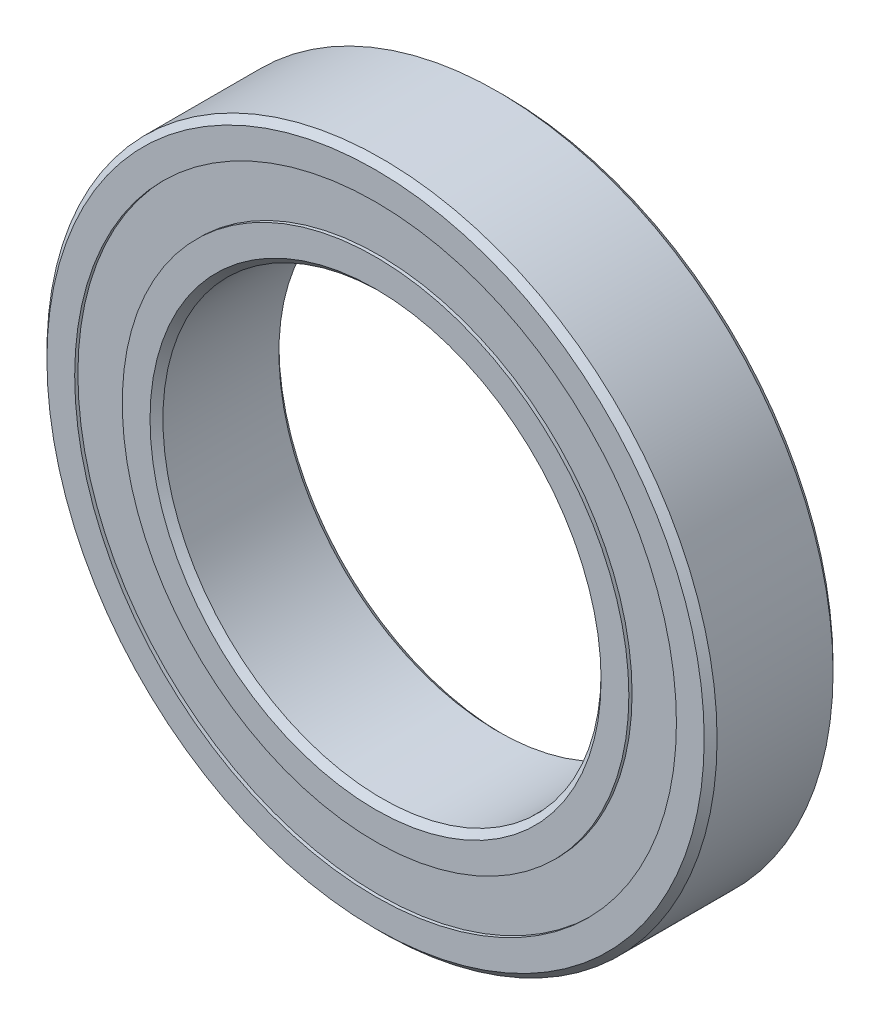
SolidWorks part; units mm, degrees
ref_plane "Front Plane" through (0, 0, 0) normal (0, 0, 1) x (1, 0, 0)
ref_plane "Top Plane" through (0, 0, 0) normal (0, 1, 0) x (1, 0, 0)
ref_plane "Right Plane" through (0, 0, 0) normal (1, 0, 0) x (0, 0, -1)
sketch "Sketch1" plane through (0, 0, 0) normal (0, 0, 1) x (1, 0, 0)
  circle A0 centre (0, 0) radius 13 construction
  circle A1 centre (0, 0) radius 8.5 construction
  dimension "OD" = 26
  dimension "Shaft Dia" = 17
sketch "Sketch2" plane through (0, 0, 0) normal (1, 0, 0) x (0, 0, -1)
  line L0 (-2.5, 0) -> (2.5, 0) construction
  line L1 (0, 13) -> (0, -13) construction
  line L2 (2.25, 13) -> (-2.25, 13) construction
  line L3 (-2.25, 13) -> (-2.5, 12.75) construction
  line L4 (-2.5, 12.75) -> (-2.5, 11.6731) construction
  line L5 (-2.5, 11.6731) -> (-1.1111, 11.6731) construction
  line L6 (2.5, 11.6731) -> (1.1111, 11.6731) construction
  line L7 (2.5, 12.75) -> (2.5, 11.6731) construction
  line L8 (2.25, 13) -> (2.5, 12.75) construction
  line L9 (0, 13) -> (0, 10.75) construction
  line L10 (0, 10.75) -> (0, 8.5) construction
  line L11 (2.5, 10.75) -> (-2.5, 10.75) construction
  line L12 (-2.5, 8.75) -> (-2.5, 9.8269) construction
  line L13 (-2.25, 8.5) -> (-2.5, 8.75) construction
  line L14 (2.25, 8.5) -> (-2.25, 8.5) construction
  line L15 (2.25, 8.5) -> (2.5, 8.75) construction
  line L16 (2.5, 8.75) -> (2.5, 9.8269) construction
  line L17 (2.5, 9.8269) -> (1.1111, 9.8269) construction
  line L18 (-2.5, 9.8269) -> (-1.1111, 9.8269) construction
  arc A0 (-1.1111, 11.6731) -> (1.1111, 11.6731) centre (0, 10.75) cw construction
  arc A1 (-1.1111, 9.8269) -> (1.1111, 9.8269) centre (0, 10.75) ccw construction
  point P14 (0, 8.5)
  point P18 (0, 10.75)
  dimension "D1" = 45
  dimension "D2" = 0.25
  dimension "D3" = 2.2222
  dimension "D4" = 0.9231
  dimension "Width" = 5
sketch "Sketch6" plane through (0, 0, 0) normal (1, 0, 0) x (0, 0, -1)
  line L0 (-2.5, 12.75) -> (-2.5, 11.6731) construction
  line L1 (-2.25, 13) -> (-2.5, 12.75) construction
  line L2 (2.25, 13) -> (-2.25, 13) construction
  line L3 (2.25, 13) -> (2.5, 12.75) construction
  line L4 (2.5, 12.75) -> (2.5, 11.6731) construction
  line L5 (2.5, 11.6731) -> (1.1111, 11.6731) construction
  line L6 (-2.5, 11.6731) -> (-1.1111, 11.6731) construction
  line L7 (-2.5, 12.75) -> (-2.5, 11.6731)
  line L8 (-2.25, 13) -> (-2.5, 12.75)
  line L9 (2.25, 13) -> (-2.25, 13)
  line L10 (2.25, 13) -> (2.5, 12.75)
  line L11 (2.5, 12.75) -> (2.5, 11.6731)
  line L12 (2.5, 11.6731) -> (1.1111, 11.6731)
  line L13 (-2.5, 11.6731) -> (-1.1111, 11.6731)
  line L14 (-2.5, 8.75) -> (-2.5, 9.8269) construction
  line L15 (-2.25, 8.5) -> (-2.5, 8.75) construction
  line L16 (2.25, 8.5) -> (-2.25, 8.5) construction
  line L17 (2.25, 8.5) -> (2.5, 8.75) construction
  line L18 (2.5, 8.75) -> (2.5, 9.8269) construction
  line L19 (2.5, 9.8269) -> (1.1111, 9.8269) construction
  line L20 (-2.5, 9.8269) -> (-1.1111, 9.8269) construction
  line L21 (-2.5, 8.75) -> (-2.5, 9.8269)
  line L22 (-2.25, 8.5) -> (-2.5, 8.75)
  line L23 (2.25, 8.5) -> (-2.25, 8.5)
  line L24 (2.25, 8.5) -> (2.5, 8.75)
  line L25 (2.5, 8.75) -> (2.5, 9.8269)
  line L26 (2.5, 9.8269) -> (1.1111, 9.8269)
  line L27 (-2.5, 9.8269) -> (-1.1111, 9.8269)
  arc A0 (1.1111, 11.6731) -> (-1.1111, 11.6731) centre (0, 10.75) ccw construction
  arc A1 (1.1111, 11.6731) -> (-1.1111, 11.6731) centre (0, 10.75) ccw
  arc A2 (-1.1111, 9.8269) -> (1.1111, 9.8269) centre (0, 10.75) ccw construction
  arc A3 (-1.1111, 9.8269) -> (1.1111, 9.8269) centre (0, 10.75) ccw
revolve "Revolve1" add sketch "Sketch6" angle 360 about L0
sketch "Sketch4" plane through (0, 0, 0) normal (1, 0, 0) x (0, 0, -1)
  line L0 (-1.4445, 10.75) -> (1.4445, 10.75)
  arc A2 (-1.4445, 10.75) -> (1.4445, 10.75) centre (0, 10.75) cw
  arc A3 (1.1111, 11.6731) -> (-1.1111, 11.6731) centre (0, 10.75) ccw construction
revolve "Revolve2" add sketch "Sketch4" angle 360 about L0
ref_axis "Axis1" through (0, 0, -2.5) along (0, 0, 1)
pattern_circular "CirPattern1" count 12 every 30 about axis through (0, 0, -2.5) along (0, 0, 1) of bodies 104
sketch "Sketch5" plane through (0, 0, 0) normal (1, 0, 0) x (0, 0, -1)
  line L0 (-2.5, 11.6731) -> (-1.1111, 11.6731) construction
  line L1 (-2.375, 11.6731) -> (-1.4445, 11.6731)
  line L2 (-2.375, 11.6731) -> (-2.375, 9.8269)
  line L3 (-2.375, 9.8269) -> (-1.4445, 9.8269)
  line L4 (-1.4445, 11.6731) -> (-1.4445, 9.8269)
  line L6 (2.5, 11.6731) -> (1.1111, 11.6731) construction
  line L7 (2.375, 11.6731) -> (1.4445, 11.6731)
  line L8 (2.375, 11.6731) -> (2.375, 9.8269)
  line L9 (2.375, 9.8269) -> (1.4445, 9.8269)
  line L10 (1.4445, 11.6731) -> (1.4445, 9.8269)
  line L12 (-2.25, 13) -> (-2.5, 12.75) construction
  line L13 (-2.5, 9.8269) -> (-1.1111, 9.8269) construction
  line L14 (2.5, 9.8269) -> (1.1111, 9.8269) construction
  point P18 (-2.375, 12.875)
revolve "Revolve3" add sketch "Sketch5" angle 360 about L0
equation "\"D2@Sketch2\"= \"Width@Sketch2\" * .05"
equation "\"D3@Sketch2\"=\"Width@Sketch2\" / 2.25"
equation "\"D4@Sketch2\"= ( ( ( \"OD@Sketch1\" - \"Width@Sketch2\" ) / 2 ) / 3.25 ) / 3.5"
equation "\"D2@CirPattern1\" = 360/\"Balls@CirPattern1\""
